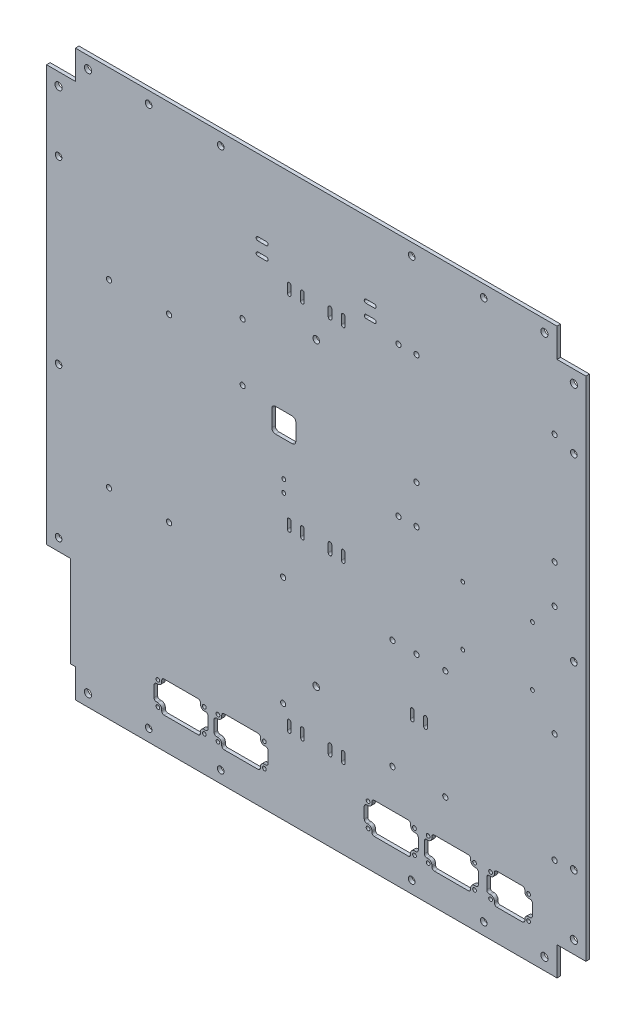
SolidWorks part; units mm, degrees
material "Acrylic (Medium-high impact)"
ref_plane "Front" through (0, 0, 0) normal (0, 0, 1) x (1, 0, 0)
ref_plane "Top" through (0, 0, 0) normal (0, 1, 0) x (1, 0, 0)
ref_plane "Right" through (0, 0, 0) normal (1, 0, 0) x (0, 0, -1)
sketch "Sketch2" plane through (0, 0, 0) normal (0, 0, 1) x (1, 0, 0)
  line L1 (0, 0) -> (449, 0)
  line L2 (0, 0) -> (0, 470)
  line L3 (0, 470) -> (449, 470)
  line L4 (449, 0) -> (449, 470)
  dimension "D1" = 449
  dimension "D2" = 470
extrude "Boss-Extrude1" add sketch "Sketch2" along normal blind 3
sketch "Sketch23" plane through (0, 0, 0) normal (0, 0, -1) x (-1, 0, 0)
  line L0 (-449, 470) -> (0, 470) construction
  line L1 (-449, 470) -> (-429, 470)
  line L2 (-449, 470) -> (-449, 450)
  line L3 (-449, 450) -> (-429, 450)
  line L4 (-429, 470) -> (-429, 450)
  line L5 (0, 470) -> (-20, 470)
  line L6 (0, 470) -> (0, 450)
  line L7 (0, 450) -> (-20, 450)
  line L8 (-20, 470) -> (-20, 450)
  line L9 (0, 470) -> (0, 0) construction
  line L11 (0, 0) -> (-20, 0)
  line L12 (0, 0) -> (0, 20)
  line L13 (0, 20) -> (-20, 20)
  line L14 (-20, 0) -> (-20, 20)
  line L15 (-449, 0) -> (-429, 0)
  line L16 (-449, 0) -> (-449, 20)
  line L17 (-449, 20) -> (-429, 20)
  line L18 (-429, 0) -> (-429, 20)
  dimension "D1" = 20
  dimension "D2" = 20
hole_wizard "M5 Clearance Hole1" positions "Sketch4" profile "Sketch5" hole size "M5" standard "ANSI Metric" end condition up to next
sketch "Sketch4" plane through (0, 0, 0) normal (0, 0, -1) x (-1, 0, 0)
  line L0 (-224.5, 470) -> (-224.5, 0) construction
  line L1 (-449, 470) -> (0, 470) construction
  line L2 (0, 0) -> (-449, 0) construction
  line L3 (-429, 460) -> (-364, 460) construction
  line L6 (-364, 460) -> (-85, 460) construction
  line L7 (-85, 460) -> (-20, 460) construction
  line L9 (-449, 235) -> (0, 235) construction
  line L10 (-449, 0) -> (-449, 470) construction
  line L12 (0, 470) -> (0, 0) construction
  line L13 (-439, 450) -> (-439, 20) construction
  line L18 (-10, 450) -> (-10, 20) construction
  line L21 (-429, 10) -> (-20, 10) construction
  line L31 (-20, 470) -> (-20, 450) construction
  line L32 (-429, 470) -> (-429, 450) construction
  line L33 (-449, 450) -> (-429, 450) construction
  line L34 (-449, 20) -> (-429, 20) construction
  line L35 (-429, 0) -> (-429, 20) construction
  line L36 (0, 450) -> (-20, 450) construction
  line L37 (0, 20) -> (-20, 20) construction
  line L38 (-20, 0) -> (-20, 20) construction
  point P13 (-224.5, 360)
  point P17 (-224.5, 110)
  point P24 (-364, 460)
  point P29 (-85, 460)
  point P54 (-304, 460)
  point P56 (-145, 460)
  point P59 (-85, 10)
  point P60 (-145, 10)
  point P61 (-304, 10)
  point P62 (-364, 10)
  point P83 (-439, 385)
  point P85 (-439, 85)
  point P92 (-10, 110)
  point P93 (-10, 385)
  point P97 (-439, 235)
  point P103 (-10, 235)
  point P147 (-10, 20)
  point P150 (-10, 34.1707)
  point P151 (-10, 20)
  point P154 (-10, 450)
  point P157 (-20, 460)
  point P160 (-429, 460)
  point P163 (-439, 450)
  point P166 (-439, 20)
  point P169 (-429, 10)
  point P172 (0, 0)
  point P173 (-10, 450)
  point P176 (-10, 20)
  point P179 (-20, 10)
  dimension "D5" = 65
  dimension "D8" = 65
  dimension "D3" = 100
  dimension "D2" = 100
  dimension "D1" = 60
  dimension "D4" = 60
  dimension "D6" = 90
  dimension "D9" = 65
sketch "Sketch5" plane through (10, 235, 0) normal (1, 0, 0) x (0, 1, 0)
  line L0 (0, 0) -> (0, 3)
  line L1 (0, 3) -> (2.75, 3)
  line L2 (2.75, 3) -> (2.75, 0)
  line L5 (2.75, 0) -> (0, 0)
  line L11 (0, -6.35) -> (0, 107.95) construction
  dimension "Thru Hole Dia." = 5.5
  dimension "Thru Hole Depth" = 3
sketch "Sketch10" plane through (0, 0, 0) normal (0, 0, -1) x (-1, 0, 0)
  line L0 (-20, 20) -> (-429, 20) construction
  line L1 (-134.5, 26) -> (-89.5, 26) construction
  line L2 (-134.5, 26) -> (-134.5, 52) construction
  line L3 (-134.5, 52) -> (-89.5, 52) construction
  line L4 (-89.5, 26) -> (-89.5, 52) construction
  line L7 (-224.5, 20) -> (-224.5, 145.1565) construction
  line L8 (-128.15, 52) -> (-128.15, 45.65)
  line L15 (-139.5, 52) -> (-184.5, 52) construction
  line L16 (-139.5, 52) -> (-139.5, 26) construction
  line L17 (-139.5, 26) -> (-184.5, 26) construction
  line L18 (-184.5, 52) -> (-184.5, 26) construction
  line L22 (-128.15, 45.65) -> (-134.5, 45.65)
  line L23 (-134.5, 45.65) -> (-134.5, 32.35)
  line L24 (-134.5, 32.35) -> (-128.15, 32.35)
  line L25 (-128.15, 32.35) -> (-128.15, 26)
  line L26 (-128.15, 26) -> (-95.85, 26)
  line L27 (-95.85, 26) -> (-95.85, 32.35)
  line L28 (-95.85, 32.35) -> (-89.5, 32.35)
  line L29 (-89.5, 32.35) -> (-89.5, 45.65)
  line L30 (-89.5, 45.65) -> (-95.85, 45.65)
  line L31 (-95.85, 45.65) -> (-95.85, 52)
  line L32 (-95.85, 52) -> (-128.15, 52)
  line L33 (-178.15, 52) -> (-178.15, 45.65)
  line L34 (-178.15, 45.65) -> (-184.5, 45.65)
  line L35 (-184.5, 45.65) -> (-184.5, 32.35)
  line L36 (-184.5, 32.35) -> (-178.15, 32.35)
  line L37 (-178.15, 32.35) -> (-178.15, 26)
  line L38 (-178.15, 26) -> (-145.85, 26)
  line L39 (-145.85, 26) -> (-145.85, 32.35)
  line L40 (-145.85, 32.35) -> (-139.5, 32.35)
  line L41 (-139.5, 32.35) -> (-139.5, 45.65)
  line L42 (-139.5, 45.65) -> (-145.85, 45.65)
  line L43 (-145.85, 45.65) -> (-145.85, 52)
  line L44 (-145.85, 52) -> (-178.15, 52)
  line L45 (-264.5, 52) -> (-264.5, 26) construction
  line L46 (-309.5, 26) -> (-264.5, 26) construction
  line L47 (-309.5, 52) -> (-309.5, 26) construction
  line L48 (-309.5, 52) -> (-264.5, 52) construction
  line L49 (-359.5, 26) -> (-359.5, 52) construction
  line L50 (-314.5, 52) -> (-359.5, 52) construction
  line L51 (-314.5, 26) -> (-314.5, 52) construction
  line L52 (-314.5, 26) -> (-359.5, 26) construction
  line L53 (-303.15, 52) -> (-270.85, 52)
  line L54 (-303.15, 45.65) -> (-303.15, 52)
  line L55 (-309.5, 45.65) -> (-303.15, 45.65)
  line L56 (-309.5, 32.35) -> (-309.5, 45.65)
  line L57 (-303.15, 32.35) -> (-309.5, 32.35)
  line L58 (-303.15, 26) -> (-303.15, 32.35)
  line L59 (-270.85, 26) -> (-303.15, 26)
  line L60 (-270.85, 32.35) -> (-270.85, 26)
  line L61 (-264.5, 32.35) -> (-270.85, 32.35)
  line L62 (-264.5, 45.65) -> (-264.5, 32.35)
  line L63 (-270.85, 45.65) -> (-264.5, 45.65)
  line L64 (-270.85, 52) -> (-270.85, 45.65)
  line L65 (-353.15, 52) -> (-320.85, 52)
  line L66 (-353.15, 45.65) -> (-353.15, 52)
  line L67 (-359.5, 45.65) -> (-353.15, 45.65)
  line L68 (-359.5, 32.35) -> (-359.5, 45.65)
  line L69 (-353.15, 32.35) -> (-359.5, 32.35)
  line L70 (-353.15, 26) -> (-353.15, 32.35)
  line L71 (-320.85, 26) -> (-353.15, 26)
  line L72 (-320.85, 32.35) -> (-320.85, 26)
  line L73 (-314.5, 32.35) -> (-320.85, 32.35)
  line L74 (-314.5, 45.65) -> (-314.5, 32.35)
  line L75 (-320.85, 45.65) -> (-314.5, 45.65)
  line L76 (-320.85, 52) -> (-320.85, 45.65)
  line L77 (0, 0) -> (-449, 0) construction
  point P6 (-429, 20)
  point P7 (-20, 20)
  point P8 (0, 0)
  point P75 (-20, 20)
  dimension "D1" = 6.35
  dimension "D2" = 45
  dimension "D3" = 40
  dimension "D4" = 26
  dimension "D5" = 5
  dimension "D6" = 26
extrude "extruder panel cutouts" cut sketch "Sketch10" against normal through all
sketch "Sketch16" plane through (0, 0, 0) normal (0, 0, -1) x (-1, 0, 0)
  line L0 (-353.15, 26) -> (-320.85, 26) construction
  line L1 (-366.5, 26) -> (-404.5, 26) construction
  line L2 (-366.5, 26) -> (-366.5, 52) construction
  line L3 (-366.5, 52) -> (-404.5, 52) construction
  line L4 (-404.5, 26) -> (-404.5, 52) construction
  line L6 (-398.15, 52) -> (-398.15, 45.65)
  line L7 (-398.15, 45.65) -> (-404.5, 45.65)
  line L8 (-404.5, 45.65) -> (-404.5, 32.35)
  line L9 (-404.5, 32.35) -> (-398.15, 32.35)
  line L10 (-398.15, 32.35) -> (-398.15, 26)
  line L11 (-398.15, 26) -> (-372.85, 26)
  line L12 (-372.85, 26) -> (-372.85, 32.35)
  line L13 (-372.85, 32.35) -> (-366.5, 32.35)
  line L14 (-366.5, 32.35) -> (-366.5, 45.65)
  line L15 (-366.5, 45.65) -> (-372.85, 45.65)
  line L16 (-372.85, 45.65) -> (-372.85, 52)
  line L17 (-372.85, 52) -> (-398.15, 52)
  line L18 (-449, 0) -> (-449, 470) construction
  dimension "D1" = 26
  dimension "D2" = 38
  dimension "D3" = 44.5
  dimension "D4" = 6.35
extrude "z_motor_panel_cutout" cut sketch "Sketch16" against normal blind 10
fillet "Fillet1" radius 3.175 20 edges at (95.85, 45.65, 1.5) (95.85, 32.35, 1.5) (128.15, 32.35, 1.5) (128.15, 45.65, 1.5) (178.15, 32.35, 1.5) (178.15, 45.65, 1.5) (145.85, 32.35, 1.5) (145.85, 45.65, 1.5) (353.15, 45.65, 1.5) (353.15, 32.35, 1.5) (320.85, 32.35, 1.5) (320.85, 45.65, 1.5) (303.15, 32.35, 1.5) (303.15, 45.65, 1.5) (270.85, 32.35, 1.5) (270.85, 45.65, 1.5) (398.15, 32.35, 1.5) (372.85, 45.65, 1.5) (372.85, 32.35, 1.5) (398.15, 45.65, 1.5)
sketch "Sketch17" plane through (0, 0, 0) normal (0, 0, -1) x (-1, 0, 0)
  circle A0 centre (-401.325, 48.825) radius 1.55
  circle A1 centre (-369.675, 48.825) radius 1.55
  circle A2 centre (-369.675, 29.175) radius 1.55
  circle A3 centre (-401.325, 29.175) radius 1.55
  circle A4 centre (-356.325, 48.825) radius 1.55
  circle A5 centre (-317.675, 48.825) radius 1.55
  circle A6 centre (-317.675, 29.175) radius 1.55
  circle A7 centre (-356.325, 29.175) radius 1.55
  circle A8 centre (-306.325, 48.825) radius 1.55
  circle A9 centre (-267.675, 48.825) radius 1.55
  circle A10 centre (-267.675, 29.175) radius 1.55
  circle A11 centre (-306.325, 29.175) radius 1.55
  circle A12 centre (-181.325, 48.825) radius 1.55
  circle A13 centre (-142.675, 48.825) radius 1.55
  circle A14 centre (-142.675, 29.175) radius 1.55
  circle A15 centre (-181.325, 29.175) radius 1.55
  circle A16 centre (-131.325, 48.825) radius 1.55
  circle A17 centre (-92.675, 48.825) radius 1.55
  circle A18 centre (-92.675, 29.175) radius 1.55
  circle A19 centre (-131.325, 29.175) radius 1.55
  dimension "D1" = 3.1
extrude "Cut-Extrude3" cut sketch "Sketch17" against normal through all
sketch "Sketch7" plane through (0, 0, 0) normal (0, 0, -1) x (-1, 0, 0)
  line L0 (-449, 0) -> (-449, 470) construction
  line L1 (-423, 299) -> (-308, 299) construction
  line L2 (-423, 299) -> (-423, 391) construction
  line L3 (-423, 391) -> (-308, 391) construction
  line L4 (-308, 299) -> (-308, 391) construction
  line L5 (-423, 299) -> (-308, 391) construction
  line L6 (-423, 391) -> (-308, 299) construction
  line L7 (-304, 295) -> (-427, 295) construction
  line L8 (-304, 295) -> (-304, 395) construction
  line L9 (-304, 395) -> (-427, 395) construction
  line L10 (-427, 295) -> (-427, 395) construction
  line L11 (-304, 295) -> (-427, 395) construction
  line L12 (-304, 395) -> (-427, 295) construction
  line L14 (-423, 175) -> (-308, 175) construction
  line L15 (-423, 175) -> (-423, 267) construction
  line L16 (-423, 267) -> (-308, 267) construction
  line L17 (-308, 175) -> (-308, 267) construction
  line L18 (-423, 175) -> (-308, 267) construction
  line L19 (-423, 267) -> (-308, 175) construction
  line L20 (-304, 171) -> (-427, 171) construction
  line L21 (-304, 171) -> (-304, 271) construction
  line L22 (-304, 271) -> (-427, 271) construction
  line L23 (-427, 171) -> (-427, 271) construction
  line L24 (-304, 171) -> (-427, 271) construction
  line L25 (-304, 271) -> (-427, 171) construction
  circle A0 centre (-423, 391) radius 2.15
  circle A1 centre (-308, 391) radius 2.15
  circle A2 centre (-308, 299) radius 2.15
  circle A3 centre (-423, 299) radius 2.15
  circle A4 centre (-423, 267) radius 2.15
  circle A5 centre (-308, 267) radius 2.15
  circle A6 centre (-308, 175) radius 2.15
  circle A7 centre (-423, 175) radius 2.15
  point P0 (-365.5, 345)
  point P6 (-365.5, 345)
  point P19 (-365.5, 221)
  point P25 (-365.5, 221)
  dimension "D5" = 4.3
  dimension "D12" = 4.3
  dimension "D1" = 115
  dimension "D2" = 92
  dimension "D3" = 123
  dimension "D4" = 100
  dimension "D6" = 22
  dimension "D7" = 55
  dimension "D8" = 115
  dimension "D9" = 92
  dimension "D10" = 123
  dimension "D11" = 100
  dimension "D13" = 24
extrude "Duet2 mounting holes" cut sketch "Sketch7" against normal through all
sketch "Sketch9" plane through (0, 0, 0) normal (0, 0, -1) x (-1, 0, 0)
  line L0 (0, 470) -> (0, 0) construction
  line L1 (-102, 167) -> (-52, 167) construction
  line L2 (-102, 167) -> (-102, 317) construction
  line L3 (-102, 317) -> (-52, 317) construction
  line L4 (-52, 167) -> (-52, 317) construction
  line L5 (-102, 167) -> (-52, 317) construction
  line L6 (-102, 317) -> (-52, 167) construction
  line L8 (0, 0) -> (-449, 0) construction
  line L9 (-20, 135) -> (-134, 135) construction
  line L10 (-20, 135) -> (-20, 349) construction
  line L11 (-20, 349) -> (-134, 349) construction
  line L12 (-134, 135) -> (-134, 349) construction
  line L13 (-20, 135) -> (-134, 349) construction
  line L14 (-20, 349) -> (-134, 135) construction
  circle A0 centre (-52, 317) radius 2.2
  circle A1 centre (-102, 317) radius 2.2
  circle A2 centre (-52, 167) radius 2.2
  circle A3 centre (-102, 167) radius 2.2
  point P0 (-77, 242)
  point P11 (-77, 242)
  point P21 (-77, 317)
  dimension "D1" = 50
  dimension "D3" = 4.4
  dimension "D2" = 114
  dimension "D4" = 32
  dimension "D5" = 150
  dimension "D6" = 20
  dimension "D7" = 135
extrude "psu mounting holes" cut sketch "Sketch9" against normal through all
sketch "Sketch11" plane through (0, 0, 0) normal (0, 0, -1) x (-1, 0, 0)
  line L0 (-224.5, 0) -> (-224.5, 150.8562) construction
  line L1 (0, 0) -> (-449, 0) construction
  line L2 (-163.25, 296.4) -> (-163.25, 344.4) construction
  circle A0 centre (-163.25, 344.4) radius 2.15
  circle A1 centre (-163.25, 296.4) radius 2.15
  dimension "D1" = 48
  dimension "D2" = 4.3
  dimension "D3" = 296.4
  dimension "D4" = 61.25
extrude "ssr holes" cut sketch "Sketch11" against normal through all
sketch "Sketch18" plane through (0, 0, 0) normal (0, 0, -1) x (-1, 0, 0)
  line L0 (-423, 267) -> (-293, 267) construction
  line L1 (-423, 391) -> (-293, 391) construction
  line L2 (-428, 396) -> (-288, 396) construction
  line L3 (-423, 391) -> (-293, 391) construction
  line L4 (-423, 391) -> (-423, 267) construction
  line L5 (-423, 267) -> (-293, 267) construction
  line L6 (-293, 391) -> (-293, 267) construction
  line L7 (-288, 396) -> (-288, 262) construction
  line L8 (-428, 262) -> (-288, 262) construction
  line L9 (-428, 396) -> (-428, 262) construction
  line L10 (-404.5, 246.5) -> (-346.5, 246.5) construction
  line L11 (-428, 250) -> (-343, 250) construction
  line L12 (-428, 250) -> (-428, 194) construction
  line L13 (-428, 194) -> (-343, 194) construction
  line L14 (-343, 250) -> (-343, 194) construction
  line L15 (-346.5, 246.5) -> (-346.5, 197.5) construction
  line L16 (-346.5, 197.5) -> (-404.5, 197.5) construction
  line L17 (-404.5, 197.5) -> (-404.5, 246.5) construction
  line L18 (-423, 84) -> (-423, 175) construction
  line L19 (-427.5, 79.5) -> (-327.5, 79.5) construction
  line L20 (-427.5, 79.5) -> (-427.5, 179.5) construction
  line L21 (-427.5, 179.5) -> (-327.5, 179.5) construction
  line L22 (-327.5, 79.5) -> (-327.5, 179.5) construction
  line L23 (-423, 175) -> (-332, 175) construction
  line L24 (-332, 84) -> (-332, 175) construction
  line L25 (-423, 84) -> (-332, 84) construction
  line L26 (-192.5, 179.5) -> (-292.5, 179.5) construction
  line L27 (-197, 175) -> (-288, 175) construction
  line L28 (-197, 175) -> (-197, 84) construction
  line L29 (-197, 84) -> (-288, 84) construction
  line L30 (-288, 175) -> (-288, 84) construction
  line L31 (-292.5, 179.5) -> (-292.5, 79.5) construction
  line L32 (-192.5, 79.5) -> (-292.5, 79.5) construction
  line L33 (-192.5, 179.5) -> (-192.5, 79.5) construction
  circle A0 centre (-293, 391) radius 2.15
  circle A1 centre (-423, 391) radius 2.15 construction
  circle A2 centre (-293, 267) radius 2.15
  circle A3 centre (-404.5, 246.5) radius 1.6
  circle A4 centre (-346.5, 246.5) radius 1.6
  circle A5 centre (-346.5, 197.5) radius 1.6
  circle A6 centre (-404.5, 197.5) radius 1.6
  circle A7 centre (-332, 175) radius 2.15
  circle A8 centre (-332, 84) radius 2.15
  circle A9 centre (-423, 84) radius 2.15
  circle A10 centre (-423, 175) radius 2.15 construction
  circle A11 centre (-288, 175) radius 2.15
  circle A12 centre (-288, 84) radius 2.15
  circle A13 centre (-197, 84) radius 2.15
  circle A14 centre (-163.25, 344.4) radius 2.15 construction
  circle A15 centre (-197, 175) radius 2.15
  dimension "D2" = 4.3
  dimension "D11" = 3.2
  dimension "D1" = 130
  dimension "D3" = 124
  dimension "D5" = 85
  dimension "D6" = 56
  dimension "D8" = 3.5
  dimension "D9" = 3.5
  dimension "D10" = 58
  dimension "D12" = 12
  dimension "D7" = 3.5
  dimension "D14" = 100
  dimension "D16" = 91
  dimension "D13" = 14.5
  dimension "D17" = 91
  dimension "D19" = 35
  dimension "D4" = 5
  dimension "D15" = 4.5
  dimension "D18" = 4.5
extrude "Duet3, Expanders, and Raspi Holes" cut sketch "Sketch18" against normal through all
sketch "Sketch12" plane through (0, 0, 0) normal (0, 0, -1) x (-1, 0, 0)
  line L0 (-414.5, 460) -> (-429, 460) construction
  line L2 (-20, 460) -> (-34.5, 460) construction
  line L4 (-439, 450) -> (-439, 435.5) construction
  line L6 (-439, 20) -> (-439, 34.5) construction
  line L8 (-429, 10) -> (-414.5, 10) construction
  line L10 (-20, 10) -> (-34.5, 10) construction
  line L12 (-10, 20) -> (-10, 34.5) construction
  line L14 (-10, 450) -> (-10, 435.5) construction
  line L19 (-429, 0) -> (-429, 20) construction
  circle A0 centre (-414.5, 460) radius 3
  circle A1 centre (-34.5, 460) radius 3
  circle A2 centre (-439, 435.5) radius 3
  circle A3 centre (-439, 34.5) radius 3
  circle A4 centre (-414.5, 10) radius 3
  circle A5 centre (-34.5, 10) radius 3
  circle A6 centre (-10, 34.5) radius 3
  circle A7 centre (-10, 435.5) radius 3
  point P4 (0, 0)
  point P5 (0, 0)
  point P7 (-10, 20)
  point P8 (-20, 10)
  point P12 (0, 0)
  point P13 (0, 0)
  point P17 (-439, 20)
  point P18 (-429, 10)
  point P22 (0, 0)
  point P23 (0, 0)
  point P32 (0, 0)
  point P33 (-10, 450)
  point P37 (0, 0)
  point P38 (-20, 460)
  point P40 (0, 0)
  point P41 (-429, 460)
  point P42 (0, 0)
  point P48 (-439, 450)
  dimension "D1" = 14.5
  dimension "D2" = 6
extrude "inside corner bracket screw clearance holes" cut sketch "Sketch12" against normal through all
sketch "Sketch6" plane through (0, 0, 0) normal (0, 0, -1) x (-1, 0, 0)
  line L0 (-224.5, 470) -> (-224.5, 0) construction
  line L1 (-449, 470) -> (0, 470) construction
  line L2 (0, 0) -> (-449, 0) construction
  line L3 (-234.5, 470) -> (-234.5, 0) construction
  line L4 (-429, 450) -> (-20, 450) construction
  line L5 (-245.5, 220) -> (-245.5, 210)
  line L6 (-234.5, 390) -> (-237.5, 390)
  line L7 (-234.5, 390) -> (-234.5, 380)
  line L8 (-234.5, 380) -> (-237.5, 380)
  line L9 (-237.5, 390) -> (-237.5, 380)
  line L10 (-245.5, 390) -> (-248.5, 390)
  line L11 (-245.5, 390) -> (-245.5, 380)
  line L12 (-245.5, 380) -> (-248.5, 380)
  line L13 (-248.5, 390) -> (-248.5, 380)
  line L14 (-245.5, 220) -> (-248.5, 220)
  line L15 (-248.5, 220) -> (-248.5, 210)
  line L16 (-245.5, 210) -> (-248.5, 210)
  line L17 (-234.5, 220) -> (-234.5, 210)
  line L18 (-234.5, 220) -> (-237.5, 220)
  line L19 (-237.5, 220) -> (-237.5, 210)
  line L20 (-234.5, 210) -> (-237.5, 210)
  line L69 (-214.5, 210) -> (-211.5, 210)
  line L70 (-211.5, 220) -> (-211.5, 210)
  line L71 (-214.5, 220) -> (-211.5, 220)
  line L72 (-214.5, 220) -> (-214.5, 210)
  line L73 (-203.5, 210) -> (-200.5, 210)
  line L74 (-200.5, 220) -> (-200.5, 210)
  line L75 (-203.5, 220) -> (-200.5, 220)
  line L76 (-200.5, 390) -> (-200.5, 380)
  line L77 (-203.5, 380) -> (-200.5, 380)
  line L78 (-203.5, 390) -> (-203.5, 380)
  line L79 (-203.5, 390) -> (-200.5, 390)
  line L80 (-211.5, 390) -> (-211.5, 380)
  line L81 (-214.5, 380) -> (-211.5, 380)
  line L82 (-214.5, 390) -> (-214.5, 380)
  line L83 (-214.5, 390) -> (-211.5, 390)
  line L84 (-203.5, 220) -> (-203.5, 210)
  line L85 (-245.5, 75) -> (-245.5, 65)
  line L86 (-245.5, 65) -> (-248.5, 65)
  line L87 (-248.5, 75) -> (-248.5, 65)
  line L88 (-245.5, 75) -> (-248.5, 75)
  line L89 (-234.5, 75) -> (-234.5, 65)
  line L90 (-234.5, 65) -> (-237.5, 65)
  line L91 (-237.5, 75) -> (-237.5, 65)
  line L92 (-234.5, 75) -> (-237.5, 75)
  line L93 (-214.5, 65) -> (-211.5, 65)
  line L98 (-211.5, 75) -> (-211.5, 65)
  line L99 (-214.5, 75) -> (-211.5, 75)
  line L104 (-214.5, 75) -> (-214.5, 65)
  line L105 (-174.5, 407) -> (-174.5, 410)
  line L106 (-274.5, 396) -> (-264.5, 396)
  line L107 (-274.5, 396) -> (-274.5, 399)
  line L108 (-274.5, 399) -> (-264.5, 399)
  line L109 (-264.5, 396) -> (-264.5, 399)
  line L110 (-264.5, 407) -> (-274.5, 407)
  line L111 (-264.5, 407) -> (-264.5, 410)
  line L112 (-264.5, 410) -> (-274.5, 410)
  line L113 (-274.5, 407) -> (-274.5, 410)
  line L114 (-184.5, 410) -> (-174.5, 410)
  line L115 (-184.5, 407) -> (-184.5, 410)
  line L116 (-184.5, 407) -> (-174.5, 407)
  line L117 (-184.5, 396) -> (-184.5, 399)
  line L118 (-174.5, 399) -> (-184.5, 399)
  line L119 (-174.5, 396) -> (-174.5, 399)
  line L120 (-174.5, 396) -> (-184.5, 396)
  line L121 (-245.5, 50) -> (-245.5, 40) [skipped]
  line L122 (-245.5, 50) -> (-248.5, 50) [skipped]
  line L123 (-248.5, 50) -> (-248.5, 40) [skipped]
  line L124 (-245.5, 40) -> (-248.5, 40) [skipped]
  line L125 (-234.5, 50) -> (-234.5, 40) [skipped]
  line L126 (-234.5, 50) -> (-237.5, 50) [skipped]
  line L127 (-237.5, 50) -> (-237.5, 40) [skipped]
  line L128 (-234.5, 40) -> (-237.5, 40) [skipped]
  line L129 (-203.5, 65) -> (-200.5, 65)
  line L130 (-200.5, 75) -> (-200.5, 65)
  line L131 (-203.5, 75) -> (-200.5, 75)
  line L132 (-203.5, 75) -> (-203.5, 65)
  line L133 (-315.5, 129.5) -> (-327.5, 129.5) construction
  line L136 (-327.5, 79.5) -> (-327.5, 179.5) construction
  line L137 (-317, 124.5) -> (-314, 124.5)
  line L138 (-317, 124.5) -> (-317, 134.5)
  line L139 (-317, 134.5) -> (-314, 134.5)
  line L140 (-314, 124.5) -> (-314, 134.5)
  line L141 (-317, 124.5) -> (-314, 134.5) construction
  line L142 (-317, 134.5) -> (-314, 124.5) construction
  line L143 (-306, 124.5) -> (-303, 124.5)
  line L144 (-306, 124.5) -> (-306, 134.5)
  line L145 (-306, 134.5) -> (-303, 134.5)
  line L146 (-303, 124.5) -> (-303, 134.5)
  line L147 (-306, 124.5) -> (-303, 134.5) construction
  line L148 (-306, 134.5) -> (-303, 124.5) construction
  line L149 (-315.5, 129.5) -> (-304.5, 129.5) construction
  line L150 (-304.5, 129.5) -> (-292.5, 129.5) construction
  line L151 (-292.5, 179.5) -> (-292.5, 79.5) construction
  point P80 (-429, 450)
  point P82 (-315.5, 129.5)
  point P87 (-304.5, 129.5)
  point P112 (0, 0)
  point P113 (0, 0)
  point P114 (-21.5507, 450)
  point P115 (-38.798, 450)
  point P116 (-20, 450)
  dimension "D1" = 10
  dimension "D3" = 3
  dimension "D4" = 8
  dimension "D6" = 60
  dimension "D11" = 8
  dimension "D12" = 60
  dimension "D13" = 40
  dimension "D7" = 170
  dimension "D9" = 145
  dimension "D10" = 8
  dimension "D8" = 2
extrude "main wiring tie-downs" cut sketch "Sketch6" against normal through all
sketch "Sketch13" plane through (0, 0, 0) normal (0, 0, -1) x (-1, 0, 0)
  line L1 (-449, 0) -> (-425, 0)
  line L2 (-449, 0) -> (-449, 24)
  line L3 (-449, 24) -> (-425, 24)
  line L4 (-425, 0) -> (-425, 24)
  line L5 (0, 0) -> (-24, 0)
  line L6 (0, 0) -> (0, 24)
  line L7 (0, 24) -> (-24, 24)
  line L8 (-24, 0) -> (-24, 24)
  line L12 (-429, 0) -> (-429, 20) construction
  line L15 (-449, 470) -> (-425, 470)
  line L16 (-449, 470) -> (-449, 446)
  line L17 (-449, 446) -> (-425, 446)
  line L18 (-425, 470) -> (-425, 446)
  line L19 (0, 470) -> (-24, 470)
  line L20 (0, 470) -> (0, 446)
  line L21 (0, 446) -> (-24, 446)
  line L22 (-24, 470) -> (-24, 446)
  line L24 (-449, 20) -> (-429, 20) construction
  line L25 (0, 20) -> (-20, 20) construction
  line L26 (-449, 450) -> (-429, 450) construction
  line L27 (0, 450) -> (-20, 450) construction
  dimension "3" = 4
  dimension "D1" = 4
  dimension "D2" = 4
  dimension "D3" = 4
  dimension "D4" = 4
extrude "Cut-Extrude1" cut sketch "Sketch13" against normal through all
fillet "Fillet3" radius 2 40 edges at (89.5, 45.65, 1.5) (95.85, 52, 1.5) (95.85, 26, 1.5) (89.5, 32.35, 1.5) (134.5, 32.35, 1.5) (128.15, 26, 1.5) (134.5, 45.65, 1.5) (128.15, 52, 1.5) (145.85, 52, 1.5) (139.5, 45.65, 1.5) (184.5, 45.65, 1.5) (178.15, 52, 1.5) (184.5, 32.35, 1.5) (178.15, 26, 1.5) (139.5, 32.35, 1.5) (145.85, 26, 1.5) (264.5, 32.35, 1.5) (270.85, 26, 1.5) (264.5, 45.65, 1.5) (270.85, 52, 1.5) (303.15, 52, 1.5) (309.5, 45.65, 1.5) (303.15, 26, 1.5) (309.5, 32.35, 1.5) (320.85, 52, 1.5) (314.5, 45.65, 1.5) (353.15, 52, 1.5) (359.5, 45.65, 1.5) (359.5, 32.35, 1.5) (353.15, 26, 1.5) (314.5, 32.35, 1.5) (320.85, 26, 1.5) (372.85, 26, 1.5) (398.15, 26, 1.5) (404.5, 32.35, 1.5) (366.5, 32.35, 1.5) (366.5, 45.65, 1.5) (372.85, 52, 1.5) (404.5, 45.65, 1.5) (398.15, 52, 1.5)
fillet "Fillet4" radius 1.5 72 edges at (200.5, 210, 1.5) (211.5, 210, 1.5) (234.5, 210, 1.5) (245.5, 210, 1.5) (248.5, 210, 1.5) (237.5, 210, 1.5) (214.5, 210, 1.5) (203.5, 210, 1.5) (203.5, 220, 1.5) (214.5, 220, 1.5) (237.5, 220, 1.5) (248.5, 220, 1.5) (245.5, 220, 1.5) (234.5, 220, 1.5) (211.5, 220, 1.5) (200.5, 220, 1.5) (264.5, 399, 1.5) (264.5, 410, 1.5) (274.5, 407, 1.5) (274.5, 396, 1.5) (274.5, 399, 1.5) (274.5, 410, 1.5) (264.5, 396, 1.5) (264.5, 407, 1.5) (245.5, 380, 1.5) (234.5, 380, 1.5) (237.5, 380, 1.5) (248.5, 380, 1.5) (234.5, 390, 1.5) (245.5, 390, 1.5) (237.5, 390, 1.5) (248.5, 390, 1.5) (214.5, 390, 1.5) (211.5, 390, 1.5) (211.5, 380, 1.5) (214.5, 380, 1.5) (203.5, 380, 1.5) (203.5, 390, 1.5) (200.5, 390, 1.5) (200.5, 380, 1.5) (174.5, 396, 1.5) (174.5, 399, 1.5) (184.5, 399, 1.5) (184.5, 396, 1.5) (184.5, 407, 1.5) (174.5, 407, 1.5) (174.5, 410, 1.5) (184.5, 410, 1.5) (214.5, 65, 1.5) (211.5, 65, 1.5) (214.5, 75, 1.5) (211.5, 75, 1.5) (200.5, 75, 1.5) (203.5, 75, 1.5) (203.5, 65, 1.5) (200.5, 65, 1.5) (245.5, 65, 1.5) (248.5, 65, 1.5) (248.5, 75, 1.5) (245.5, 75, 1.5) (237.5, 65, 1.5) (234.5, 65, 1.5) (237.5, 75, 1.5) (234.5, 75, 1.5) (317, 134.5, 1.5) (314, 134.5, 1.5) (306, 134.5, 1.5) (303, 134.5, 1.5) (317, 124.5, 1.5) (314, 124.5, 1.5) (306, 124.5, 1.5) (303, 124.5, 1.5)
sketch "Sketch19" plane through (0, 0, 0) normal (0, 0, -1) x (-1, 0, 0)
  line L0 (0, 0) -> (-20, 0) construction
  line L1 (-20, 100) -> (0, 100)
  line L2 (-20, 100) -> (-20, 0)
  line L3 (-20, 0) -> (0, 0)
  line L4 (0, 100) -> (0, 0)
  line L6 (0, 446) -> (0, 24) construction
  point P4 (0, 0)
  point P8 (0, 0)
  point P10 (-20, 0)
  point P12 (0, 0)
  point P13 (0, 0)
  point P15 (0, 0)
  point P16 (-16.571, 0)
  dimension "D3" = 100
extrude "power inlet socket cutout" cut sketch "Sketch19" against normal through all
sketch "Sketch20" plane through (0, 0, 0) normal (0, 0, -1) x (-1, 0, 0)
  line L1 (-187.5, 295) -> (-207.5, 295)
  line L2 (-187.5, 295) -> (-187.5, 275)
  line L3 (-187.5, 275) -> (-207.5, 275)
  line L4 (-207.5, 295) -> (-207.5, 275)
  line L5 (-197.5, 275) -> (-197.5, 295) construction
  line L6 (-224.5, 470) -> (-224.5, 0) construction
  line L7 (-449, 235) -> (0, 235) construction
  dimension "D1" = 27
  dimension "D2" = 20
  dimension "D3" = 40
  dimension "D4" = 20
extrude "Cut-Extrude5" cut sketch "Sketch20" against normal through all
fillet "Fillet6" radius 3 4 edges at (187.5, 275, 1.5) (187.5, 295, 1.5) (207.5, 295, 1.5) (207.5, 275, 1.5)
sketch "Sketch22" plane through (0, 0, 0) normal (0, 0, -1) x (-1, 0, 0)
  line L0 (-197.5, 246) -> (-197.5, 236) construction
  line L1 (-204.5, 275) -> (-190.5, 275) construction
  line L2 (-197.5, 246) -> (-197.5, 275) construction
  circle A0 centre (-197.5, 246) radius 1.6
  circle A1 centre (-197.5, 236) radius 1.6
  dimension "D1" = 3.2
  dimension "D3" = 29
  dimension "D2" = 10
extrude "Cable Chain Attachment Points" cut sketch "Sketch22" against normal through all
equation "\"D8@Sketch4\"=\"D5@Sketch4\""
equation "\"D2@Sketch4\"=\"D3@Sketch4\""
equation "\"D11@Sketch6\"=\"D4@Sketch6\""
equation "\"D4@Sketch4\"=\"D1@Sketch4\""
equation "\"D9@Sketch18\"=\"D8@Sketch18\""
equation "\"D18@Sketch18\"=\"D15@Sketch18\""
equation "\"D10@Sketch6\"=\"D4@Sketch6\""
equation "\"D9@Sketch4\"=\"D8@Sketch4\""
equation "\"D1@Sketch13\"=\"3@Sketch13\""
equation "\"D2@Sketch13\"=\"3@Sketch13\""
equation "\"D3@Sketch13\"=\"3@Sketch13\""
equation "\"D4@Sketch13\"=\"3@Sketch13\""
